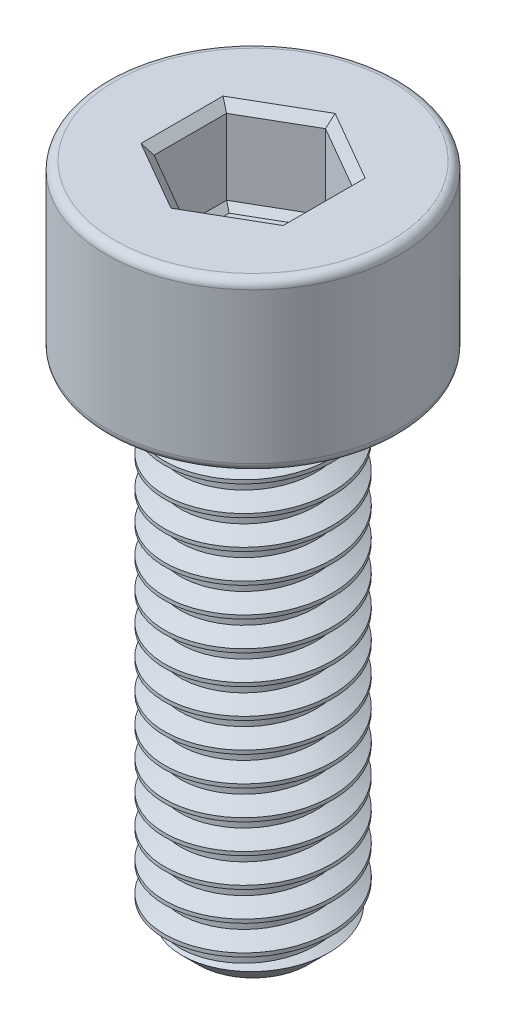
SolidWorks part; units mm, degrees
material "AISI Type A2 Tool Steel"
ref_plane "Front Plane" through (0, 0, 0) normal (0, 0, 1) x (1, 0, 0)
ref_plane "Top Plane" through (0, 0, 0) normal (0, 1, 0) x (1, 0, 0)
ref_plane "Right Plane" through (0, 0, 0) normal (1, 0, 0) x (0, 0, -1)
sketch "Sketch1" plane through (0, 0, 0) normal (0, 1, 0) x (1, 0, 0)
  circle A0 centre (0, 0) radius 2
  dimension "D1" = 4
extrude "Boss-Extrude1" add sketch "Sketch1" along normal blind 12
thread "Thread1" pitch 0.7 start angle 0, offset 1, length 0, pitch 0.7, diameter 4
ref_plane "Plane1" through (2, -1, 0) normal (0, 0, 1) x (1, 0, 0)
sketch "Thread Profile1" plane through (2, -1, 0) normal (0, 0, 1) x (1, 0, 0)
  line L0 (0, 0) -> (0, 0.7) construction
  line L11 (0, 0) -> (0, 0.6125)
  line L12 (0, 0.6125) -> (-0.3789, 0.3937)
  line L13 (-0.3789, 0.3937) -> (-0.3789, 0.2187)
  line L15 (-0.3789, 0.2187) -> (0, 0)
  line L17 (-0.3789, 0.3062) -> (0, 0.3062) construction
  point P2 (0, 0)
  dimension "Pitch" = 0.7
  dimension "Profile_Angle" = 60
  dimension "Profile_Land" = 0.175
  dimension "Profile_Height" = 0.3789
sketch "Sketch4" plane through (0, 12, 0) normal (0, -1, 0) x (-1, 0, 0)
  circle A0 centre (0, 0) radius 3.5
  dimension "D1" = 7
extrude "Boss-Extrude2" add sketch "Sketch4" against normal blind 4
fillet "Fillet1" radius 0.2 2 edges at (0, 12, -3.5) (0, 16, -3.5)
sketch "Sketch6" plane through (0, 0, 0) normal (0, 0, 1) x (1, 0, 0)
  line L0 (0, 0) -> (2.01, 0) construction
  line L1 (2.01, 0) -> (2.01, 0.7)
  line L2 (2.01, 0.7) -> (1.31, 0)
  line L3 (1.31, 0) -> (2.01, 0)
  line L4 (0, 0) -> (0, 0.3482) construction
  dimension "D1" = 0.7
  dimension "D2" = 45
  dimension "D3" = 2.01
revolve "Cut-Revolve1" cut sketch "Sketch6" angle 360 about L4
sketch "Sketch7" plane through (0, 16, 0) normal (0, 1, 0) x (1, 0, 0)
  line L1 (0, 1.7321) -> (-1.5, 0.866)
  line L2 (-1.5, 0.866) -> (-1.5, -0.866)
  line L3 (-1.5, -0.866) -> (0, -1.7321)
  line L4 (0, -1.7321) -> (1.5, -0.866)
  line L5 (1.5, -0.866) -> (1.5, 0.866)
  line L6 (1.5, 0.866) -> (0, 1.7321)
  circle A0 centre (0, 0) radius 1.5 construction
  dimension "D1" = 3
extrude "Cut-Extrude1" cut sketch "Sketch7" against normal blind 2
chamfer "Chamfer1" distance 0.2 angle 45 6 edges at (-1.5, 16, 0) (-0.75, 16, 1.299) (0.75, 16, 1.299) (1.5, 16, 0) (0.75, 16, -1.299) (-0.75, 16, -1.299)
sketch "Sketch8" plane through (0, 14, 0) normal (0, 1, 0) x (1, 0, 0)
  line L1 (0, 1.7321) -> (-1.5, 0.866)
  line L2 (-1.5, 0.866) -> (-1.5, -0.866)
  line L3 (-1.5, -0.866) -> (0, -1.7321)
  line L4 (0, -1.7321) -> (1.5, -0.866)
  line L5 (1.5, -0.866) -> (1.5, 0.866)
  line L6 (1.5, 0.866) -> (0, 1.7321)
  circle A0 centre (0, 0) radius 1.5 construction
extrude "Cut-Extrude2" cut sketch "Sketch8" against normal blind 0.15 draft 45
